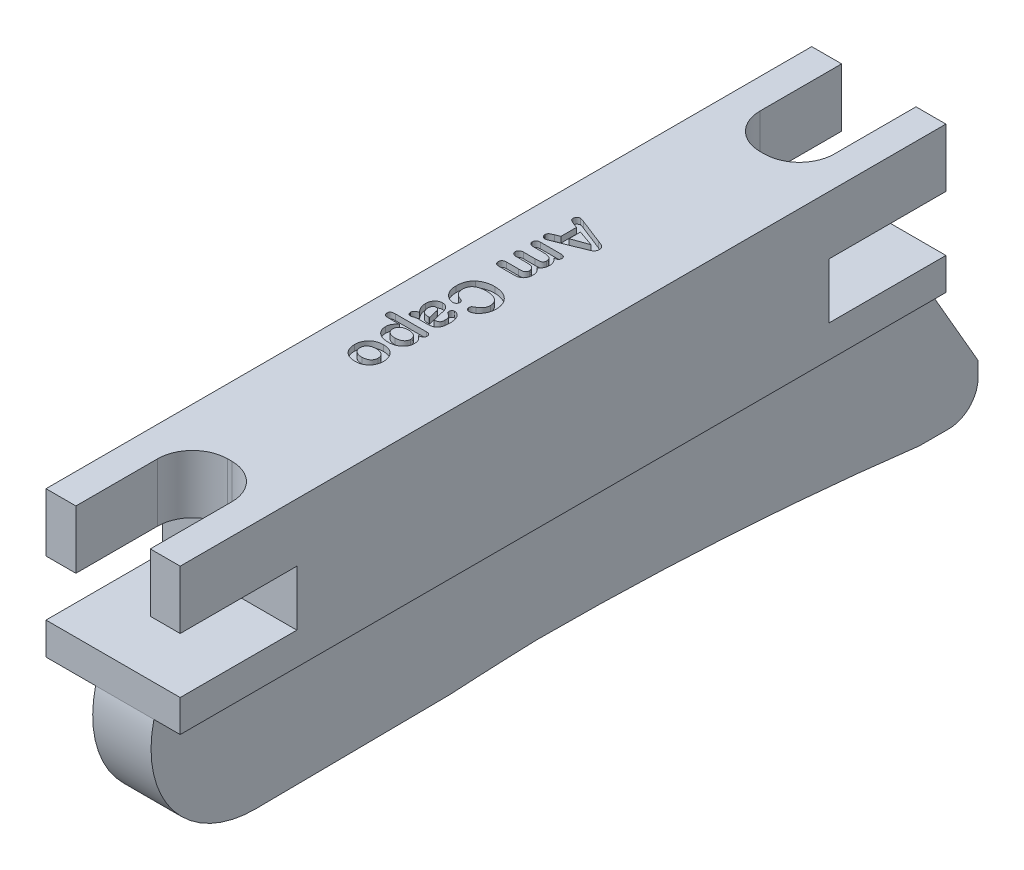
SolidWorks part; units mm, degrees
ref_plane "Front Plane" through (0, 0, 0) normal (0, 0, 1) x (1, 0, 0)
ref_plane "Top Plane" through (0, 0, 0) normal (0, 1, 0) x (1, 0, 0)
ref_plane "Right Plane" through (0, 0, 0) normal (1, 0, 0) x (0, 0, -1)
sketch "Sketch2" plane through (0, 0, 0) normal (0, 1, 0) x (1, 0, 0)
  line L1 (0, 0) -> (11.684, 0)
  line L2 (0, 0) -> (0, 66.675)
  line L3 (0, 66.675) -> (11.684, 66.675)
  line L4 (11.684, 0) -> (11.684, 66.675)
  dimension "D1" = 66.675
  dimension "D2" = 11.684
extrude "Boss-Extrude1" add sketch "Sketch2" along normal blind 12.7
sketch "Sketch3" plane through (0, 0, 0) normal (0, -1, 0) x (1, 0, 0)
  line L0 (11.684, -66.675) -> (0, -66.675) construction
  line L1 (4.318, 0) -> (9.398, 0)
  line L2 (4.318, 0) -> (4.318, -66.675)
  line L3 (4.318, -66.675) -> (9.398, -66.675) construction
  line L4 (9.398, 0) -> (9.398, -66.675)
  line L5 (0, -66.675) -> (0, 0) construction
  line L6 (0, 0) -> (11.684, 0) construction
  line L7 (4.318, 0) -> (4.318, 5.08)
  line L8 (4.318, 5.08) -> (9.398, 5.08)
  line L9 (9.398, 5.08) -> (9.398, 0)
  line L10 (4.318, -66.675) -> (4.318, -71.755)
  line L11 (4.318, -71.755) -> (9.398, -71.755)
  line L12 (9.398, -71.755) -> (9.398, -66.675)
  line M3 (0, -66.675) -> (11.684, -66.675)
  line M5 (11.684, 0) -> (0, 0)
  dimension "D1" = 5.08
  dimension "D2" = 4.318
  dimension "D3" = 5.08
extrude "Boss-Extrude2" add sketch "Sketch3" along normal blind 12.7 contours L4 L2 M5 M3 | L11 L12 L10 M3 | L9 L8 L7 M5 region at (6.858, 0, 2.54) region at (6.858, 0, -33.3375) region at (6.858, 0, -69.215)
sketch "Sketch4" plane through (0, 0, 0) normal (0, 0, 1) x (1, 0, 0)
  line L0 (0, 12.7) -> (11.684, 12.7) construction
  line L1 (0, 7.62) -> (2.6035, 7.62)
  line L2 (0, 7.62) -> (0, 2.794)
  line L3 (0, 2.794) -> (11.684, 2.794)
  line L4 (11.684, 7.62) -> (11.684, 2.794)
  line L5 (2.6035, 12.7) -> (9.0805, 12.7)
  line L6 (2.6035, 12.7) -> (2.6035, 7.62)
  line L8 (9.0805, 12.7) -> (9.0805, 7.62)
  line L9 (9.0805, 7.62) -> (11.684, 7.62)
  line L10 (11.684, 12.7) -> (11.684, 0) construction
  line L11 (0, 12.7) -> (0, 0) construction
  point P10 (5.842, 12.7)
  dimension "D2" = 6.477
  dimension "D3" = 4.826
  dimension "D4" = 5.08
extrude "Cut-Extrude1" cut sketch "Sketch4" against normal blind 10.16
ref_plane "Plane1" through (0, 0, -33.3375) normal (0, 0, 1) x (1, 0, 0)
fillet "Fillet2" radius 3.048 2 edges at (9.0805, 10.16, -10.16) (2.6035, 10.16, -10.16)
mirror "Mirror1" about plane through (0, 0, -33.3375) normal (0, 0, 1) of "Fillet2", "Cut-Extrude1"
sketch "Sketch5" plane through (4.318, 0, 0) normal (-1, 0, 0) x (0, 0, 1)
  line L0 (-33.3375, -10.668) -> (-33.3375, -12.7) construction
  line L2 (-66.675, -12.7) -> (0, -12.7)
  line L3 (5.08, -12.7) -> (-71.755, -12.7) construction
  arc A0 (-66.675, -12.7) -> (0, -12.7) centre (-33.3375, -285.1557) cw
  dimension "D1" = 2.032
extrude "Cut-Extrude4" cut sketch "Sketch5" against normal through all
sketch "Sketch6" plane through (0, 12.7, 0) normal (0, 1, 0) x (1, 0, 0)
  line L0 (2.6035, 7.112) -> (2.6035, 59.563) construction
  arc A0 (5.6515, 10.16) -> (2.6035, 7.112) centre (5.6515, 7.112) ccw construction
  text T0 "Am Capo\r\n\r\n\r\n" font "Arial Rounded MT Bold" height 3.5
extrude "Cut-Extrude5" cut sketch "Sketch6" against normal blind 0.508
chamfer "Chamfer1" distance 5.08 angle 60 2 edges at (6.858, 0, 5.08) (6.858, 0, -71.755) first distance on face at (6.858, 0, 2.54) first distance on face at (6.858, 0, -69.215)
sketch "Sketch7" plane through (4.318, 0, 0) normal (-1, 0, 0) x (0, 0, 1)
  line L0 (0, -13.716) -> (5.08, -13.716)
  line L1 (5.08, -13.716) -> (5.08, -12.3672)
  line L2 (5.08, -12.7) -> (0, -12.7) construction
  line L3 (5.08, -12.7) -> (0, -12.7)
  arc A0 (-33.3375, -10.668) -> (0, -13.716) centre (-42.4956, -294.6731) cw
  arc A1 (0, -12.7) -> (-66.675, -12.7) centre (-33.3375, -285.1557) ccw construction
  arc A2 (0, -12.7) -> (-66.675, -12.7) centre (-33.3375, -285.1557) ccw
  point P10 (0, -13.716)
  point P11 (0, -13.716)
  point P12 (-33.3375, -10.668)
  arc M7 (-66.675, -12.7) -> (0, -12.7) centre (-33.3375, -285.1557) cw
  line M8 (0, -12.7) -> (5.08, -12.7)
  dimension "D2" = 13.208
  dimension "D1" = 1.016
extrude "Boss-Extrude3" add sketch "Sketch7" against normal up to surface (5.08 mm away) contours A0 L0 L1 M7 M8 region at (4.318, -12.2913, -8.0471) up to face at (9.398, -8.2957, -33.3375)
fillet "Fillet3" radius 2.54 2 edges at (6.858, -12.7, -71.755) (6.858, -13.716, 5.08)
sketch "Sketch8" plane through (4.318, 0, 0) normal (-1, 0, 0) x (0, 0, 1)
  line L0 (-33.3375, 0) -> (-33.3375, -10.668)
  line L2 (-8.89, -11.176) -> (-25.7764, -11.0127)
  line L9 (-71.755, -8.7988) -> (-71.755, -10.16)
  line L10 (-69.215, -12.7) -> (-66.675, -12.7)
  line L11 (0, -13.716) -> (2.54, -13.716)
  line L12 (5.08, -11.176) -> (5.08, -8.7988)
  line L13 (5.08, -8.7988) -> (0, 0)
  line L14 (0, 0) -> (-66.675, 0)
  line L15 (-66.675, 0) -> (-71.755, -8.7988)
  line L16 (-71.755, -8.7988) -> (-71.755, -10.16)
  line L17 (-69.215, -12.7) -> (-66.675, -12.7)
  line L18 (0, -13.716) -> (2.54, -13.716)
  line L19 (5.08, -11.176) -> (5.08, -8.7988)
  line L20 (5.08, -8.7988) -> (0, 0)
  line L21 (0, 0) -> (-66.675, 0)
  line L22 (-66.675, 0) -> (-71.755, -8.7988)
  arc A2 (-8.89, -11.176) -> (0, 0) centre (-8.8024, -2.1219) ccw
  arc A6 (-71.755, -10.16) -> (-69.215, -12.7) centre (-69.215, -10.16) ccw
  arc A7 (-33.3375, -10.668) -> (-66.675, -12.7) centre (-33.3375, -285.1557) ccw
  arc A8 (0, -13.716) -> (-33.3375, -10.668) centre (-42.4956, -294.6731) ccw
  arc A9 (2.54, -13.716) -> (5.08, -11.176) centre (2.54, -11.176) ccw
  arc A10 (-71.755, -10.16) -> (-69.215, -12.7) centre (-69.215, -10.16) ccw
  arc A11 (-33.3375, -10.668) -> (-66.675, -12.7) centre (-33.3375, -285.1557) ccw
  arc A12 (0, -13.716) -> (-33.3375, -10.668) centre (-42.4956, -294.6731) ccw
  arc A13 (2.54, -13.716) -> (5.08, -11.176) centre (2.54, -11.176) ccw
  arc M6 (-33.3375, -10.668) -> (0, -13.716) centre (-42.4956, -294.6731) cw
  line M7 (0, -13.716) -> (2.54, -13.716)
  arc M8 (2.54, -13.716) -> (5.08, -11.176) centre (2.54, -11.176) ccw
  line M9 (5.08, -11.176) -> (5.08, -8.7988)
  line M10 (5.08, -8.7988) -> (0, 0)
  dimension "D2" = 0
  dimension "D1" = 11.176
  dimension "D3" = 0.554
  dimension "D4" = 8.89
extrude "Cut-Extrude7" cut sketch "Sketch8" against normal through all contours A2 L2 M6 M7 M8 M9 M10 region at (4.318, -9.8025, -1.6346)
